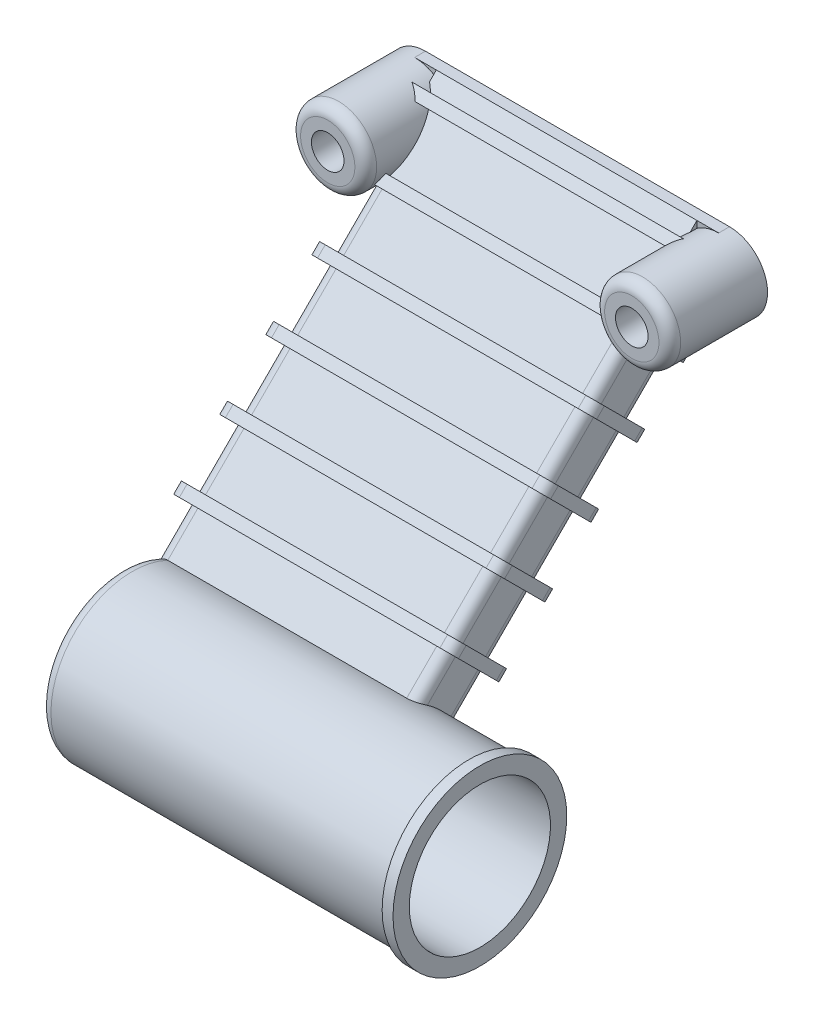
SolidWorks part; units mm, degrees
material "Gray Cast Iron"
ref_plane "Front" through (0, 0, 0) normal (0, 0, 1) x (1, 0, 0)
ref_plane "Top" through (0, 0, 0) normal (0, 1, 0) x (1, 0, 0)
ref_plane "Right" through (0, 0, 0) normal (1, 0, 0) x (0, 0, -1)
sketch "Sketch1" plane through (0, 0, 0) normal (0, 0, 1) x (1, 0, 0)
  line L0 (-14, 0) -> (14, 0) construction
  line L1 (-14, 0) -> (14, 0) construction
  line L2 (-14, 3.5) -> (14, 3.5)
  line L3 (-14, -3.5) -> (14, -3.5)
  arc A0 (-14, 3.5) -> (-14, -3.5) centre (-14, 0) ccw
  arc A1 (14, -3.5) -> (14, 3.5) centre (14, 0) ccw
  point P3 (0, 0)
  dimension "D1" = 14
  dimension "D2" = 14
extrude "Boss-Extrude6" add sketch "Sketch1" along normal blind 1
sketch "Sketch6" plane through (0, 0, 1) normal (0, 0, 1) x (1, 0, 0)
  circle A0 centre (-14, 0) radius 3.5
  circle A1 centre (14, 0) radius 3.5
extrude "Boss-Extrude7" add sketch "Sketch6" along normal blind 8
sketch "Sketch7" plane through (0, 0, 9) normal (0, 0, 1) x (1, 0, 0)
  circle A0 centre (-14, 0) radius 1.5
  circle A1 centre (14, 0) radius 1.5
extrude "Cut-Extrude2" cut sketch "Sketch7" against normal blind 9
sketch "Sketch8" plane through (0, 0, 0) normal (0, 0, -1) x (-1, 0, 0)
  line L0 (-12.5, 0) -> (12.5, 0) construction
  line L2 (-11, 2.5) -> (11, 2.5)
  line L3 (-11, 2.5) -> (-11, -2.5)
  line L4 (-11, -2.5) -> (11, -2.5)
  line L5 (11, 2.5) -> (11, -2.5)
  line L6 (-11, 2.5) -> (11, -2.5) construction
  line L7 (-11, -2.5) -> (11, 2.5) construction
  circle A0 centre (-14, 0) radius 1.5 construction
  circle A1 centre (14, 0) radius 1.5 construction
  point P7 (0, 0)
extrude "Cut-Extrude3" cut sketch "Sketch8" against normal blind 1
sketch "Sketch9" plane through (0, 0, 0) normal (1, 0, 0) x (0, 0, -1)
  line L0 (-1, 3.5) -> (-1, -3.5)
  line L4 (-31.7379, -27.2448) -> (-28.2448, -30.7379)
  line L5 (-31.7379, -27.2448) -> (-1, 3.5)
  line L6 (-1, -3.5) -> (-28.2448, -30.7379)
extrude "Boss-Extrude8" add sketch "Sketch9" along normal blind 12 and the other way blind 12
sketch "Sketch10" plane through (0, -29.4914, 29.4914) normal (0, -0.7071, 0.7071) x (1, 0, 0)
  line L0 (-11, 2.6771) -> (11, 2.6771)
  line L1 (11, 2.6771) -> (11, -1.2678)
  line L2 (11, -1.2678) -> (-11, -1.2678)
  line L3 (-11, -1.2678) -> (-11, 2.6771)
  line L5 (12, -1.3239) -> (12, 3.181) construction
  line L7 (-12, 3.1771) -> (12, 3.1771) construction
  line L10 (-12, -1.7678) -> (12, -1.7678) construction
  dimension "D1" = 22
  dimension "D2" = 0.5
  dimension "D3" = 0.5
  dimension "D4" = 1
ref_plane "Plane1" through (0, -25.9558, 25.9558) normal (0, -0.7071, 0.7071) x (1, 0, 0)
sketch "Sketch11" plane through (0, -25.9558, 25.9558) normal (0, -0.7071, 0.7071) x (1, 0, 0)
  line L0 (-13, 4.1771) -> (13, 4.1771)
  line L1 (13, 4.1771) -> (13, -2.7629)
  line L2 (13, -2.7629) -> (-13, -2.7629)
  line L3 (-13, -2.7629) -> (-13, 4.1771)
  line L4 (-12, 3.1771) -> (12, 3.1771) construction
  line L5 (-12, -1.7629) -> (12, -1.7629) construction
  line L6 (-12, -1.3239) -> (-12, 3.181) construction
  line L7 (12, -1.3239) -> (12, 3.181) construction
  dimension "D1" = 1
  dimension "D2" = 1
  dimension "D3" = 1
  dimension "D4" = 1
extrude "Boss-Extrude9" add sketch "Sketch11" against normal blind 1
fillet "Fillet1" radius 1 4 edges at (13, -22.6486, 28.556) (13, -27.556, 23.6486) (-13, -27.556, 23.6486) (-13, -22.6486, 28.556)
fillet "Fillet2" radius 1 8 edges at (-12, -14.9979, 12.5008) (12, -14.9979, 12.5008) (12, -28.9704, 26.4768) (-12, -28.9704, 26.4768) (-12, -25.4769, 29.9704) (12, -25.4769, 29.9704) (-12, -12.937, 17.4333) (12, -12.937, 17.4333)
pattern_linear "LPattern6" count 5 spacing 6 along (0, 0.7072, -0.707) of "Boss-Extrude9", "Fillet1"
ref_plane "Plane2" through (0, -4.7426, 4.7426) normal (0, 0.7071, -0.7071) x (-1, 0, 0)
sketch "Sketch12" plane through (0, -4.7426, 4.7426) normal (0, 0.7071, -0.7071) x (-1, 0, 0)
  line L1 (-12.999, 3.6161) -> (-12.999, -2.7629)
  line L3 (13, -2.7629) -> (13.0009, 3.4891)
  line L5 (-12.999, -2.7629) -> (13, -2.7629)
  line L6 (13.0009, 3.4891) -> (12.3613, 4.1771)
  line L7 (-12.2362, 4.1771) -> (-12.999, 3.6158)
  line L8 (-12.2362, 4.1771) -> (12.3613, 4.1771)
  ellipse E0 centre (14, 6.364) end of major axis (17.5, 6.364) minor radius 2.4749 construction
extrude "Boss-Extrude10" add sketch "Sketch12" along normal blind 1 contours L8 L7 L1 L5 L3 L6 | L7 L8 L6 L3 L5 L1 region at (-0.0003, -4.2482, 5.2371)
fillet "Fillet3" radius 1 2 edges at (12.999, -6.3427, 2.4354) (-13, -6.3427, 2.4354)
ref_plane "Plane3" through (0, -0.5, 0.5) normal (0, 0.7071, -0.7071) x (1, 0, 0)
sketch "Sketch13" plane through (0, -0.5, 0.5) normal (0, 0.7071, -0.7071) x (1, 0, 0)
  line L0 (12.9999, -4.1771) -> (-13.0001, -4.1771)
  line L1 (-13.0001, -4.1771) -> (-13.0001, -3.182)
  line L2 (-12, -3.182) -> (12, -3.182) construction
  line L3 (-13.0001, -3.182) -> (12.9999, -3.182)
  line L4 (12.9999, -3.182) -> (12.9999, -4.1771)
  line L5 (10.6714, -4.1771) -> (-10.6714, -4.1771) construction
  dimension "D1" = 0
extrude "Boss-Extrude11" add sketch "Sketch13" along normal blind 1
extrude "Cut-Extrude4" cut sketch "Sketch10" against normal blind 42 contours L0 L1 L2 L3
sketch "Sketch14" plane through (0, 0, 1) normal (0, 0, -1) x (-1, 0, 0)
  line L0 (-11, 1.4142) -> (11, 1.4142)
  line L1 (11, -2.5) -> (11, 2.5) construction
  line L2 (11, 2.1001) -> (11, -27.5984) construction
  line L3 (11, 1.4142) -> (11, 1.9642)
  line L4 (11, 1.4142) -> (11, 2.5) construction
  line L5 (11, 1.9642) -> (-11, 1.9642)
  line L6 (-11, 2.5) -> (-11, -2.5) construction
  line L7 (-11, 1.9642) -> (-11, 1.4142)
extrude "Cut-Extrude5" cut sketch "Sketch14" against normal blind 0.5
ref_plane "Plane4" through (0, -29.4914, 29.4914) normal (0, -0.7071, 0.7071) x (1, 0, 0)
sketch "Sketch15" plane through (0, -29.4914, 29.4914) normal (0, -0.7071, 0.7071) x (1, 0, 0)
  line L1 (-11, 2.6771) -> (11, 2.6771)
  line L2 (-11, 2.6771) -> (-11, -1.2678)
  line L3 (-11, -1.2678) -> (11, -1.2678)
  line L4 (11, 2.6771) -> (11, -1.2678)
  line L5 (0, -1.2678) -> (0, 2.6771) construction
  line L6 (-11, 0.7047) -> (11, 0.7047) construction
  point P308 (0, 0.7047)
sketch "Sketch16" plane through (-12, 0, 0) normal (-1, 0, 0) x (0, 0, 1)
  circle A0 centre (29.9897, -28.9931) radius 7.5
  circle A1 centre (29.9897, -28.9931) radius 6.5
extrude "Boss-Extrude12" add sketch "Sketch16" against normal blind 33
sketch "Sketch17" plane through (-12, 0, 0) normal (-1, 0, 0) x (0, 0, 1)
  circle A0 centre (29.9897, -28.9931) radius 7.5
extrude "Boss-Extrude13" add sketch "Sketch17" against normal blind 1
sketch "Sketch18" plane through (-12, 0, 0) normal (-1, 0, 0) x (0, 0, 1)
  circle A0 centre (29.9897, -28.9931) radius 7.5
extrude "Cut-Extrude6" cut sketch "Sketch18" along normal blind 1
fillet "Fillet4" radius 1 1 edges at (-12, -34.2981, 35.2912)
extrude "Cut-Extrude7" cut sketch "Sketch15" against normal blind 30 contours L4 L3 L2 L1
sketch "Sketch19" plane through (21, 0, 0) normal (1, 0, 0) x (0, 0, -1)
  circle A0 centre (-29.9897, -28.9931) radius 6.5
extrude "Cut-Extrude8" cut sketch "Sketch19" against normal blind 32
sketch "Sketch20" plane through (21, 0, 0) normal (1, 0, 0) x (0, 0, -1)
  circle A0 centre (-29.9897, -28.9931) radius 8
  circle M3 centre (-29.9897, -28.9931) radius 7.5
extrude "Boss-Extrude14" add sketch "Sketch20" against normal blind 1 contours A0 M3 region at (21, -28.9931, 37.7634)
fillet "Fillet5" radius 1 2 edges at (17.5, 0, 9) (-10.5, 0, 9)
